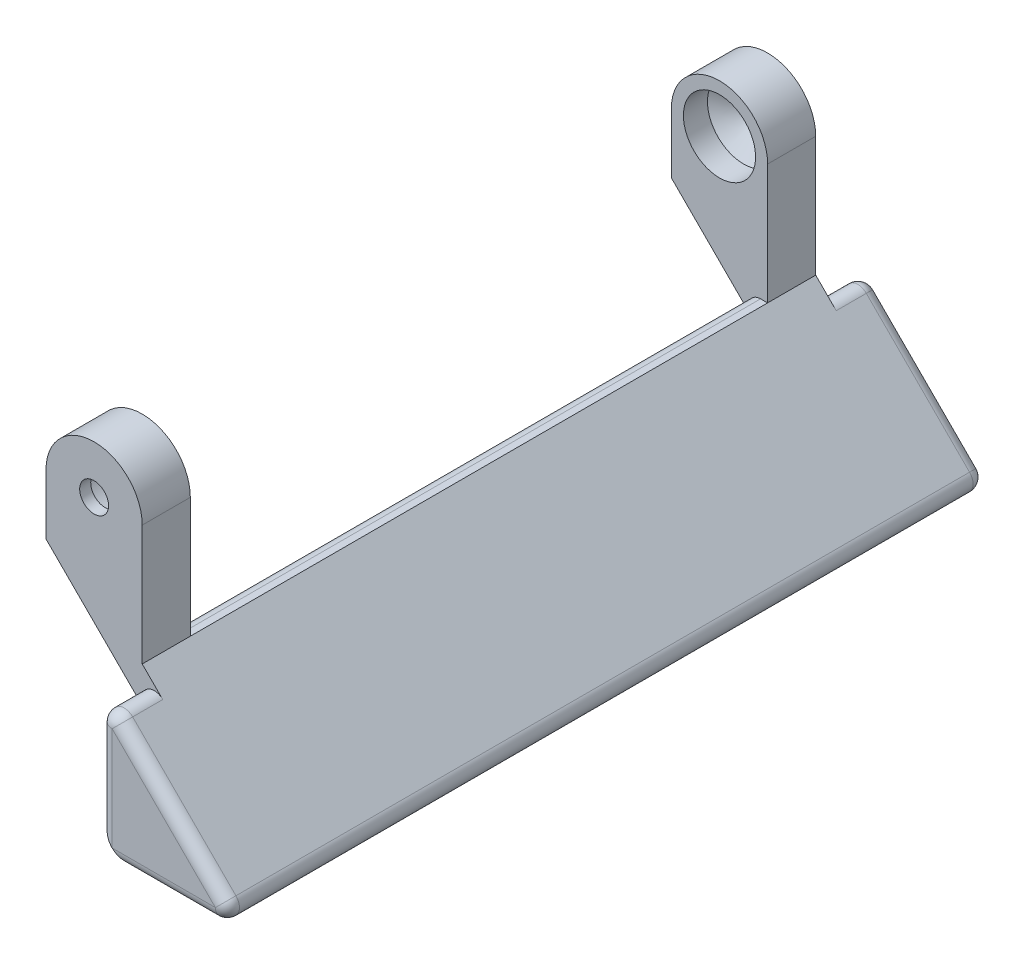
SolidWorks part; units mm, degrees
material "Liga 1060"
ref_plane "Plano frontal" through (0, 0, 0) normal (0, 0, 1) x (1, 0, 0)
ref_plane "Plano superior" through (0, 0, 0) normal (0, 1, 0) x (1, 0, 0)
ref_plane "Plano direito" through (0, 0, 0) normal (1, 0, 0) x (0, 0, -1)
sketch "Esboço1" plane through (0, 0, 0) normal (0, 0, 1) x (1, 0, 0)
  line L0 (0, 0) -> (0, 22)
  line L1 (0, 0) -> (20, 0)
  line L2 (20, 0) -> (8, 12)
  line L3 (8, 12) -> (8, 22)
  arc A0 (8, 22) -> (0, 22) centre (4, 22) ccw
  dimension "D1" = 20
  dimension "D2" = 22
  dimension "D3" = 45
  dimension "D4" = 8
extrude "Ressalto-extrusão1" add sketch "Esboço1" along normal blind 63
sketch "Esboço2" plane through (0, 0, 0) normal (-1, 0, 0) x (0, 0, 1)
  line L0 (0, 0) -> (0, 11)
  line L1 (0, 22) -> (0, 0) construction
  line L2 (0, 11) -> (21, 11)
  line L4 (63, 0) -> (0, 0) construction
  line L5 (21, 0) -> (0, 0)
  line L6 (21, 0) -> (42, 0)
  line L7 (42, 0) -> (63, 0)
  line L8 (63, 22) -> (63, 0) construction
  line L9 (63, 0) -> (63, 11)
  line L10 (63, 11) -> (42, 11)
  line L12 (21, 11) -> (42, 11)
  dimension "D1" = 11
  dimension "D2" = 21
  dimension "D3" = 21
extrude "Corte-extrusão1" cut sketch "Esboço2" against normal blind 8
sketch "Esboço3" plane through (0, 0, 0) normal (-1, 0, 0) x (0, 0, 1)
  line L0 (0, 0) -> (3.5, 0)
  line L2 (3.5, 0) -> (3.5, 26)
  line L3 (63, 26) -> (0, 26) construction
  line L4 (3.5, 26) -> (0, 26)
  line L5 (0, 26) -> (0, 0)
  line L6 (63, 0) -> (59.5, 0)
  line L7 (63, 22) -> (63, 11) construction
  line L8 (59.5, 0) -> (59.5, 26)
  line L9 (59.5, 26) -> (63, 26)
  line L10 (63, 26) -> (63, 0)
  line L12 (0, 0) -> (63, 0) construction
  line L13 (0, 22) -> (0, 11) construction
  dimension "D1" = 3.5
  dimension "D2" = 3.5
extrude "Corte-extrusão2" cut sketch "Esboço3" against normal up to surface (8 mm away) up to face at (8, 17, 31.5)
chamfer "Chanfro1" distance 2 angle 45 1 edges at (8, 0, 31.5)
chamfer "Chanfro2" distance 2 angle 45 1 edges at (8, 11, 31.5)
sketch "Esboço6" plane through (0, 0, 3.5) normal (0, 0, -1) x (-1, 0, 0)
  line L0 (-8, 12) -> (0, 20)
  line L1 (0, 11) -> (0, 22) construction
  line L2 (0, 20) -> (0, 22)
  line L3 (-8, 22) -> (-8, 12)
  line L4 (-8, 9) -> (-6, 11) construction
  line L5 (-8, 12) -> (-8, 22) construction
  arc A0 (0, 22) -> (-8, 22) centre (-4, 22) ccw
extrude "Corte-extrusão4" cut sketch "Esboço6" against normal offset from surface (48 mm away) 4 from offset 4 contours L0 L2 A0 L3 up to face at (5, 15.1667, 59.5) offset against normal yes
sketch "Esboço8" plane through (8, 0, 0) normal (1, 0, 0) x (0, 0, -1)
  line L0 (-55.5, 12) -> (-7.5, 12)
  line L1 (-7.5, 12) -> (-7.5, 20)
  line L2 (-7.5, 20) -> (-55.5, 20)
  line L3 (-55.5, 20) -> (-55.5, 12)
  line L4 (-63, 0) -> (0, 0) construction
  dimension "D1" = 12
extrude "Corte-extrusão5" cut sketch "Esboço8" against normal through all both and the other way through all
sketch "Esboço9" plane through (0, 0, 7.5) normal (0, 0, 1) x (1, 0, 0)
  line L0 (8, 22) -> (0, 22) construction
  point P4 (4, 22)
sketch "Esboço10" plane through (0, 0, 55.5) normal (0, 0, -1) x (-1, 0, 0)
  line L0 (-8, 22) -> (0, 22) construction
  point P4 (-4, 22)
hole_wizard "Furo de diâmetro Ø6.0 (6)1" positions "3DSketch3" profile "Esboço15" hole size "Ø6.0" standard "ISO"
sketch3d "3DSketch3"
  point P0 (4, 22, 7.5)
sketch "Esboço15" plane through (4, 22, 7.5) normal (1, 0, 0) x (0, -1, 0)
  line L0 (0, 0) -> (0, 3.8026)
  line L1 (0, 3.8026) -> (3, 2)
  line L2 (3, 2) -> (3, 0)
  line L5 (3, 0) -> (0, 0)
  line L10 (0, 3.8026) -> (-3, 2) construction
  line L11 (0, -6.35) -> (0, 107.95) construction
  dimension "Hole Dia." = 6
  dimension "Hole Depth" = 2
  dimension "Drill Angle" = 118
hole_wizard "Furo de diâmetro Ø6.0 (6)2" positions "3DSketch4" profile "Esboço16" hole size "Ø6.0" standard "ISO"
sketch3d "3DSketch4"
  point P0 (4, 22, 55.5)
sketch "Esboço16" plane through (4, 22, 55.5) normal (1, 0, 0) x (0, 1, 0)
  line L0 (0, 0) -> (0, 3.8026)
  line L1 (0, 3.8026) -> (3, 2)
  line L2 (3, 2) -> (3, 0)
  line L5 (3, 0) -> (0, 0)
  line L10 (0, 3.8026) -> (-3, 2) construction
  line L11 (0, -6.35) -> (0, 107.95) construction
  dimension "Hole Dia." = 6
  dimension "Hole Depth" = 2
  dimension "Drill Angle" = 118
hole_wizard "Furo com folga de M21" positions "3DSketch1" profile "Esboço11" hole size "M2" standard "ISO" end condition through all
sketch3d "3DSketch1"
  point P0 (4, 22, 55.5)
  point P3 (4, 22, 7.5)
sketch "Esboço11" plane through (4, 22, 55.5) normal (1, 0, 0) x (0, 1, 0)
  line L0 (0, 0) -> (0, 7.5)
  line L1 (0, 7.5) -> (1.2, 7.5)
  line L2 (1.2, 7.5) -> (1.2, 0)
  line L5 (1.2, 0) -> (0, 0)
  line L11 (0, -6.35) -> (0, 107.95) construction
  dimension "Thru Hole Dia." = 2.4
  dimension "Thru Hole Depth" = 7.5
sketch "Esboço12" plane through (0, 0, 59.5) normal (0, 0, 1) x (1, 0, 0)
  line L0 (0, 11) -> (6, 11)
  line L3 (6, 11) -> (0, 17)
  line L4 (6, 11) -> (0, 11) construction
  line L5 (0, 17) -> (0, 11)
  line L7 (6, 11) -> (0, 11) construction
  dimension "D2" = 45
extrude "Corte-extrusão6" cut sketch "Esboço12" against normal through all
fillet "Filete1" radius 1 1 edges at (5, 12, 31.5)
fillet "Filete3" radius 1 5 edges at (20, 0, 31.5) (14, 6, 0) (15, 0, 0) (14, 6, 63) (15, 0, 63) tangent propagation no
fillet "Filete4" radius 1 6 edges at (8, 6.2929, 0) (8, 11.5858, 0.2929) (8, 6.2929, 63) (8, 11.5858, 62.7071) (8, 12, 2.25) (8, 12, 60.75)
